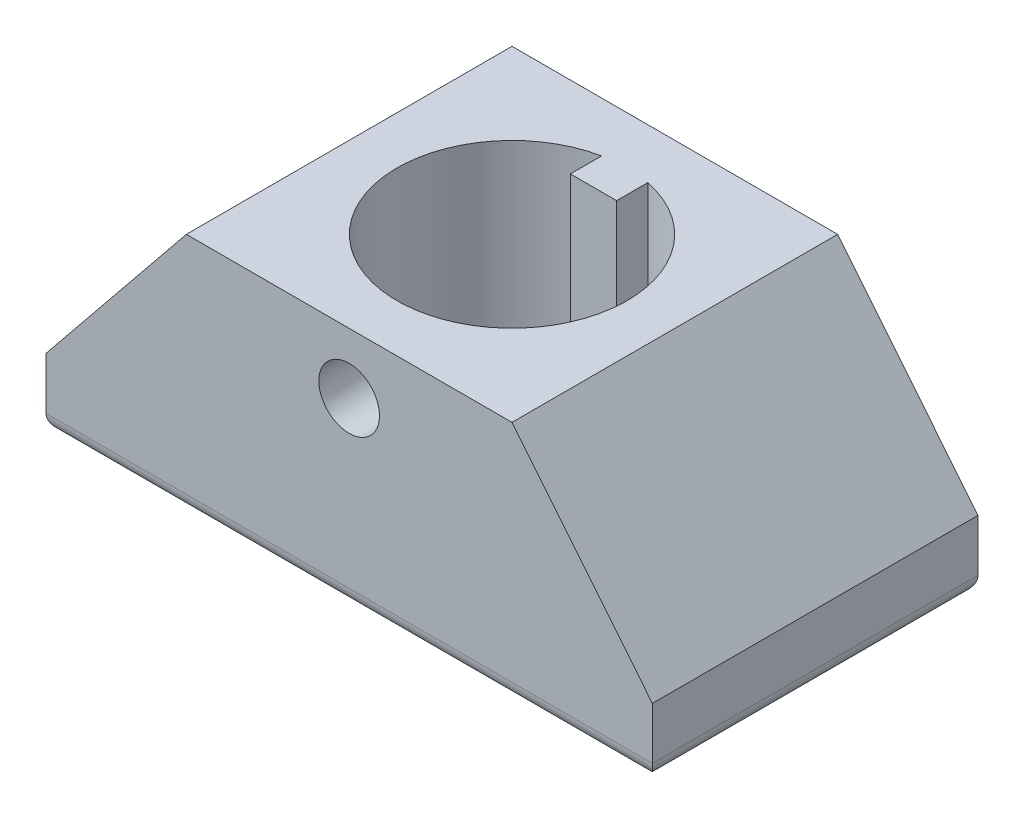
SolidWorks part; units mm, degrees
ref_plane "Front Plane" through (0, 0, 0) normal (0, 0, 1) x (1, 0, 0)
ref_plane "Top Plane" through (0, 0, 0) normal (0, 1, 0) x (1, 0, 0)
ref_plane "Right Plane" through (0, 0, 0) normal (1, 0, 0) x (0, 0, -1)
sketch "Sketch1" plane through (0, 0, 0) normal (0, 1, 0) x (1, 0, 0)
  line L0 (-1.335, 6.5044) -> (-1.335, 4.7044)
  line L1 (-1.335, 4.7044) -> (1.335, 4.7044)
  line L2 (1.335, 4.7044) -> (1.335, 6.5044)
  line L4 (-9.4, -9.4) -> (9.4, -9.4)
  line L5 (-9.4, -9.4) -> (-9.4, 9.4)
  line L6 (-9.4, 9.4) -> (9.4, 9.4)
  line L7 (9.4, -9.4) -> (9.4, 9.4)
  line L8 (-9.4, -9.4) -> (9.4, 9.4) construction
  line L9 (-9.4, 9.4) -> (9.4, -9.4) construction
  arc A1 (-1.335, 6.5044) -> (1.335, 6.5044) centre (0, 0) ccw
  dimension "D1" = 13.28
  dimension "D2" = 18.8
  dimension "D3" = 1.8
  dimension "D4" = 2.67
  dimension "D5" = 1.335
  dimension "D6" = 18.8
extrude "Boss-Extrude1" add sketch "Sketch1" along normal blind 10
sketch "Sketch5" plane through (0, 0, -4.7044) normal (0, 0, 1) x (1, 0, 0)
  line L1 (1.335, 10) -> (-1.335, 10) construction
  circle A0 centre (-0.0001, 6.5) radius 1.75
  dimension "D1" = 3.5
  dimension "D2" = 3.5
extrude "Cut-Extrude3" cut sketch "Sketch5" along normal blind 15
sketch "Sketch6" plane through (0, 0, 0) normal (0, -1, 0) x (1, 0, 0)
  line L1 (17.5, -9.4) -> (-17.5, -9.4)
  line L2 (17.5, -9.4) -> (17.5, 9.4)
  line L3 (17.5, 9.4) -> (-17.5, 9.4)
  line L4 (-17.5, -9.4) -> (-17.5, 9.4)
  line L5 (17.5, -9.4) -> (-17.5, 9.4) construction
  line L6 (17.5, 9.4) -> (-17.5, -9.4) construction
  point P0 (0, 0)
  dimension "D1" = 18.8
  dimension "D2" = 35
extrude "Boss-Extrude2" add sketch "Sketch6" along normal blind 4
sketch "Sketch7" plane through (0, 0, 9.4) normal (0, 0, 1) x (1, 0, 0)
  line L0 (-9.4, 10) -> (-9.4, 0)
  line L1 (-9.4, 0) -> (-17.5, 0)
  line L2 (-17.5, 0) -> (-9.4, 10)
  line L3 (9.4, 0) -> (17.5, 0)
  line L4 (17.5, 0) -> (9.4, 10)
  line L5 (9.4, 10) -> (9.4, 0)
extrude "Boss-Extrude3" add sketch "Sketch7" against normal up to surface (18.8 mm away) up to face at (-1.0125, 2.75, -9.4)
fillet "Fillet4" radius 1 4 edges at (17.5, -4, 0) (0, -4, -9.4) (-17.5, -4, 0) (0, -4, 9.4)
sketch "Sketch8" plane through (0, 0, 0) normal (0, 1, 0) x (1, 0, 0)
  line L0 (1.335, 4.7044) -> (-1.335, 4.7044) construction
  line L1 (1.335, 6.5044) -> (1.335, 4.7044) construction
  line L2 (-1.335, 4.7044) -> (-1.335, 6.5044) construction
  line L3 (1.335, 4.7044) -> (-1.335, 4.7044)
  line L4 (1.335, 6.5044) -> (1.335, 4.7044)
  line L5 (-1.335, 4.7044) -> (-1.335, 6.5044)
  arc A0 (-1.335, 6.5044) -> (1.335, 6.5044) centre (0, 0) ccw construction
  arc A1 (-1.335, 6.5044) -> (1.335, 6.5044) centre (0, 0) ccw
extrude "Cut-Extrude4" cut sketch "Sketch8" against normal blind 4
fillet "Fillet5" radius 0.5 4 edges at (-1.335, -4, -5.6044) (0, -4, -4.7044) (1.335, -4, -5.6044) (0, -4, 6.64)
equation "\"CageLeftBottomEdge\"=22.11mm"
equation "\"CageLeftTopEdge\"=22.11mm"
equation "\"CageRightBottomEdge\"=21.63mm"
equation "\"CageRightTopEdge\"=21.63mm"
equation "\"CageHeight\"=86.04mm"
equation "\"CageLength\"=73.76mm"
equation "\"CageTopScrewClearance\"=10mm"
equation "\"CageBottomScrewClearance\"=25mm"
equation "\"CageLeftTopDepth\"= 11.65mm"
equation "\"CageLeftBottomDepth\"=11.11mm"
equation "\"CageLeftTopHeight\"=8.56175mm"
equation "\"CageLeftBottomHeight\"=16mm"
equation "\"CageRightTopDepth\"= 11.05mm"
equation "\"CageRightBottomDepth\"=10.58mm"
equation "\"CageRightTopHeight\"=9.6mm"
equation "\"CageRightBottomHeight\"=15.49mm"
equation "\"CageLeftTopChannelDepth\"=2.41908mm"
equation "\"CageLeftBottomChannelDepth\"=2.588mm"
equation "\"CageLeftChannelHeight\"=11.7mm"
equation "\"CageRightTopChannelDepth\"=2.32mm"
equation "\"CageRightBottomChannelDepth\"=2.318mm"
equation "\"CageRightChannelHeight\"=10mm"
equation "\"CageChanRelHeight\"=23.99mm"
equation "\"CageChanRelDepth\"=5.492mm"
equation "\"CageChamberRadius\"=16.261mm"
equation "\"CageScrewDiameter\"=4.8mm"
equation "\"CageSetScrewDiameter\"=3.5mm"
equation "\"CageAxleRadius\"=6.639mm"
equation "\"CageAxleKeyHeight\"=1.619mm"
equation "\"CageAxleKeyWidth\"=2.662mm"
equation "\"CageHoseWindowWidth\"=16.29mm"
equation "\"CageHoseWindowHeight\"=26.5mm"
equation "\"CageHoseWindow-Edge\"=8.89mm"
equation "\"CageScrew-VerticalEdge\"=5.0mm"
equation "\"CageScrew-HorizontalEdge\"=7.5mm"
equation "\"CageScrew-HoseCornerScrewEdge\"=4.45mm"
equation "\"CageAxle-BottomEdge\"=56.05mm"
equation "\"CageAxle-FrontEdge\"=46.03mm"
equation "\"CageBackSetScrew-Axle\"=40mm"
equation "\"CageFrontSetScrew-Axle\"=22mm"
equation "\"CageVelocityWindow-BackEdge\"=34.8mm"
equation "\"CageVelocityWindow-BottomEdge\"=27.55mm"
equation "\"CageVelocityWindowHeight\"=22.29mm"
equation "\"CageVelocityWindowWidth\"=12.61mm"
equation "\"TriggerSlot-BottomEdge\"=6.35mm"
equation "\"TriggerSlot-FrontEdge\"=15mm"
equation "\"TriggerSlotSize\"=6.7mm"
equation "\"TriggerRackOffset\"=.236224in"
equation "\"TriggerSlotSizeInt\"=.25in"
equation "\"MotorMountLegLength\"=.25in"
equation "\"GearOffset\"=.264907in"
equation "\"TriggerSlotSpacing\"=.25in"
equation "\"TriggerMiniSlotWidth\"=3.5mm"
equation "\"TriggerRackWidth\"=6.5mm"
equation "\"TGMGearFaceDiameter\"=24.40mm"
equation "\"TGMCylinderLength\"=15.00mm"
equation "\"TGMScrewHole-Center\"=8.70mm"
equation "\"TGMScrewHoleDiameter\"=5.04mm"
equation "\"TGMCenterHoleDiameter\"=9.50mm"
equation "\"TGMShaftCollarSideLength\"=19.00mm"
equation "\"TGMShaftCollarDockingDepth\"=7.00mm"
equation "\"whitemotordepth\"=11.27mm"
equation "\"whitemotorbackdepth\"=3.845mm"
equation "\"whitemotoraxledepth\" = 3.5mm"
equation "\"whitemotoraxleoffset\"=11.4mm"
equation "\"whitemotorwidth\"=12.07mm"
equation "\"whitemotorheight\"=16.68mm"
equation "\"whitemotorcylinderlength\" =13.04mm"
equation "\"whitemotorcylinderradius\"=3.845mm"
equation "\"whitemotorcylinderoffset\"=2.35mm"
equation "\"whitemotorcutoutlength\"=1.88mm"
equation "\"whitemotorouterrad\"=5mm"
equation "\"whitemotorinnerrad\"=2.95mm"
equation "\"elasticracklength\"=2in"
equation "\"elasticrackpegsize\"=.25in"
equation "\"elasticrackpegbuffer\"=.125in"
equation "\"elasticrackpegspacing\"=1.76476378in"
equation "\"elasticbaybuffer\"=.25in"
equation "\"elasticdepth\"=.125in"
equation "\"elasticbaydepth\"=.75in"
equation "\"motormountwidth\"=12mm"
equation "\"motormountcornerfillet\"=3mm"
equation "\"pandiscradius\"=14in"
equation "\"towermaterialwidth\"=.25in"
equation "\"towerslotlength\"=.5in"
equation "\"towermarkerspace\"=5in"
equation "\"towerslothorizoffset\"=1in"
equation "\"towerslothorizspacing\"=2in"
equation "\"towerslotvertoffset\"=3in"
equation "\"towerslotvertspacing\"=2in"
equation "\"towerheight\"=12in"
equation "\"towerupslot\"=1in"
equation "\"toweraxle\"=.5in"
equation "\"towerplatslotoffset\"=1.5in"
equation "\"towermotorpanelheight\"=10in"
equation "\"towerplatdepth\"=2in"
equation "\"stepperouterrad\"=10mm"
equation "\"stepperscrewsize\"=3.45mm"
equation "\"stepperscrewc2c\"=49.5mm"
equation "\"stepperdepthoffset\"=24mm"
equation "\"stepperhorizoffset\"=22.91mm"
equation "\"shaftslotOD\"=18.8mm"
equation "\"shaftslotID\"=13.28mm"
equation "\"shaftkeywidth\"=2.67mm"
equation "\"shaftkeydepth\"=1.8mm"
equation "\"shaftcollartotaldepth\"=12.5mm"
equation "\"shaftsquaredepth\"=6mm"
equation "\"shaftsetscrewsize\"=3.5mm"
equation "\"shaftkeytightdepth\"=1.85mm"
equation "\"shaftslottightID\"=12.78mm"
equation "\"D3@Sketch1\"=\"shaftkeydepth\""
equation "\"D4@Sketch1\"=\"shaftkeywidth\""
equation "\"D5@Sketch1\"=\"shaftkeywidth\"/2"
equation "\"D1@Sketch1\"=\"shaftslotID\""
equation "\"D6@Sketch1\"=\"shaftslotOD\""
equation "\"D2@Sketch1\"=\"shaftslotOD\""
equation "\"D1@Sketch6\"=\"shaftslotOD\""
equation "\"cagecollartotaldepth\"=10mm"
equation "\"D1@Boss-Extrude1\"=\"cagecollartotaldepth\""
equation "\"D1@Sketch5\"=\"shaftsetscrewsize\""
equation "\"D2@Sketch5\"=\"shaftsetscrewsize\""
equation "\"cagecollartotalwidth\"=35mm"
equation "\"D2@Sketch6\"=\"cagecollartotalwidth\""
equation "\"cagecollarbasedepth\"=4mm"
equation "\"D1@Boss-Extrude2\"=\"cagecollarbasedepth\""
equation "\"shaftsetscrewoffset\"=9mm"
